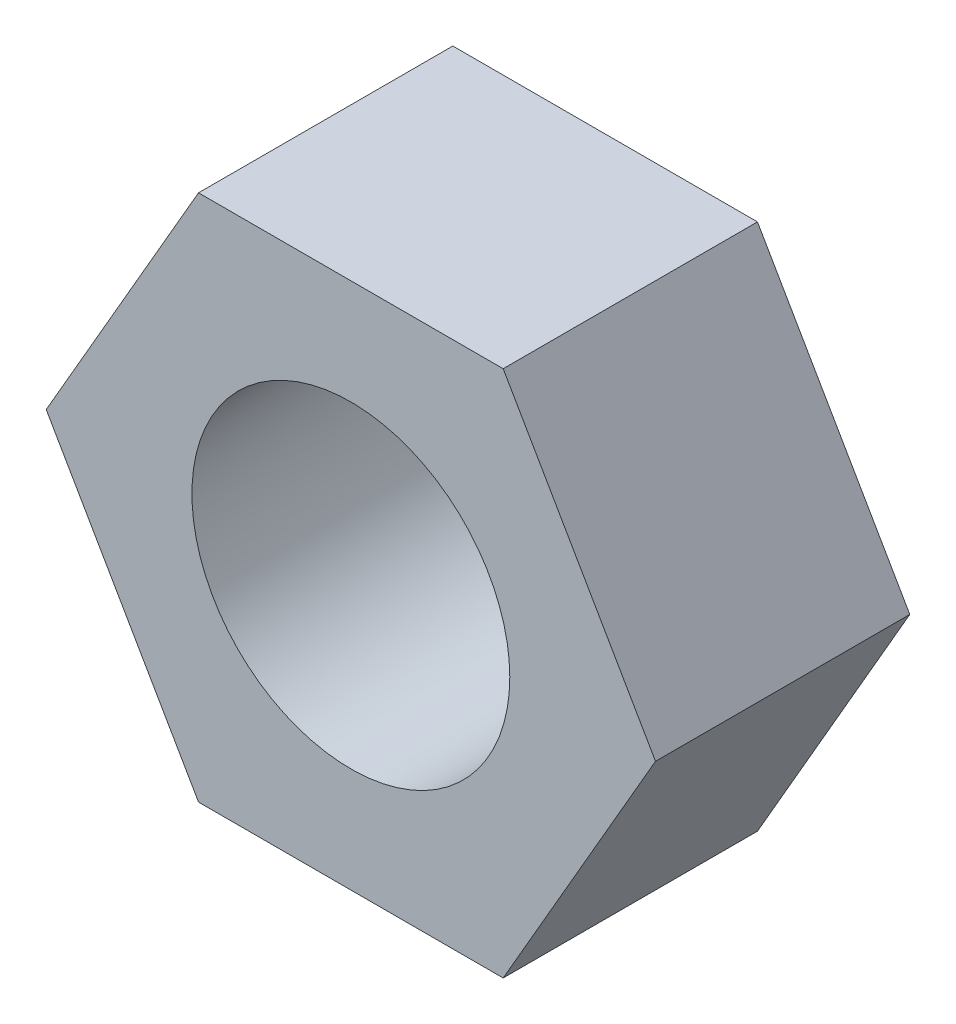
SolidWorks part; units mm, degrees
ref_plane "Спереди" through (0, 0, 0) normal (0, 0, 1) x (1, 0, 0)
ref_plane "Сверху" through (0, 0, 0) normal (0, 1, 0) x (1, 0, 0)
ref_plane "Справа" through (0, 0, 0) normal (1, 0, 0) x (0, 0, -1)
other "Configuration Table"
sketch "Шестигранник_эскиз" plane through (0, 0, 0) normal (0, 0, 1) x (1, 0, 0)
  line L0 (4.792, 0) -> (2.396, 4.15)
  line L1 (2.396, 4.15) -> (-2.396, 4.15)
  line L2 (-2.396, 4.15) -> (-4.792, 0)
  line L3 (-4.792, 0) -> (-2.396, -4.15)
  line L4 (-2.396, -4.15) -> (2.396, -4.15)
  line L5 (2.396, -4.15) -> (4.792, 0)
  circle A0 centre (0, 0) radius 4.15 construction
  point P9 (-5.2631, 0)
  point P10 (1.7888, 4.2431)
  point P11 (2.396, -4.15)
  dimension "D1" = 8.3
extrude "Корпус_гайки" add sketch "Шестигранник_эскиз" along normal blind 4
sketch "Отверстие_эскиз" plane through (0, 0, 0) normal (0, 0, 1) x (1, 0, 0)
  circle A0 centre (0, 0) radius 2.5
  dimension "D1" = 5
extrude "Отверстие_под_M5" cut sketch "Отверстие_эскиз" against normal through all and the other way through all
cosmetic thread "Резьба_M5x0_8_6H" parameters "D2"=5
equation "\"Гайка под ключ\"= 8"
equation "\"Гайка высота\"= 4"
equation "\"Гайка отверстие под резьбу\"=5"
equation "\"Гайка диаметр резьбы\"= 5"
equation "\"Гайка шаг резьбы\"= 0.8"
equation "\"Гайка фаска отверстия\"= 0.4"
equation "\"D1@Корпус_гайки\" = \"Гайка высота\""
equation "\"D1@Отверстие_эскиз\" = \"Гайка отверстие под резьбу\""
